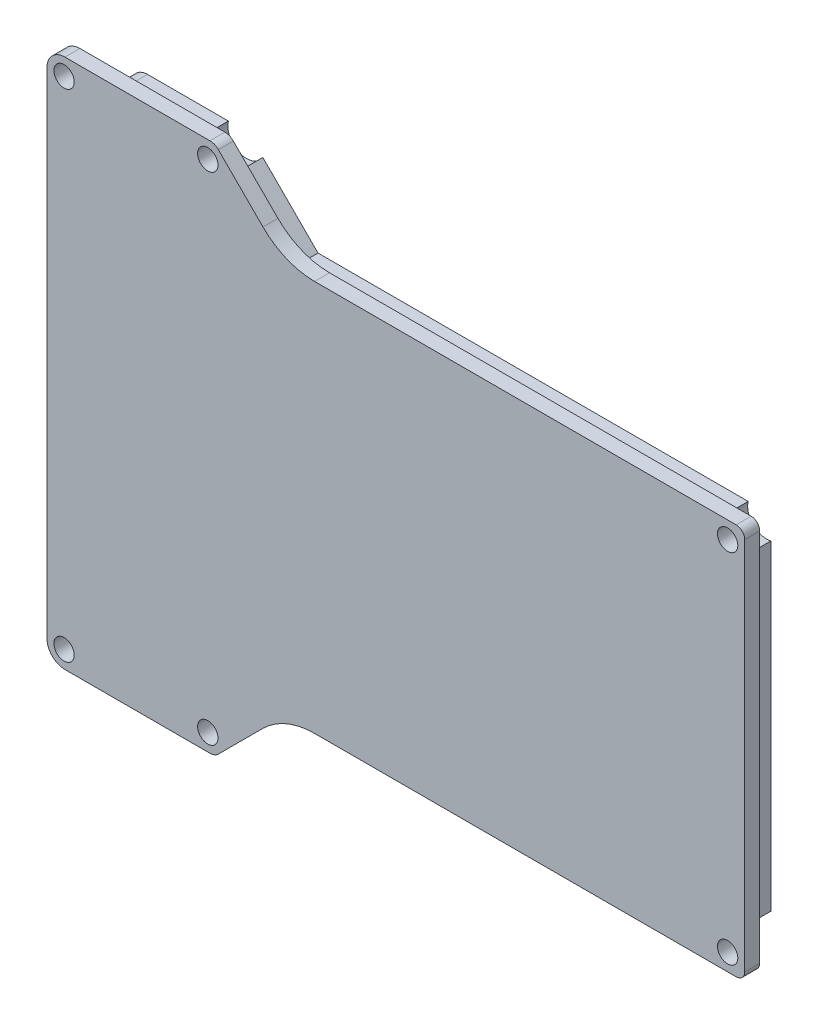
SolidWorks part; units mm, degrees
ref_plane "Front Plane" through (0, 0, 0) normal (0, 0, 1) x (1, 0, 0)
ref_plane "Top Plane" through (0, 0, 0) normal (0, 1, 0) x (1, 0, 0)
ref_plane "Right Plane" through (0, 0, 0) normal (1, 0, 0) x (0, 0, -1)
sketch "Sketch1" plane through (0, 0, 0) normal (0, 0, 1) x (1, 0, 0)
  line L0 (22, -44.3746) -> (2.3, -44.3746)
  line L1 (90.115, -44.3746) -> (105.155, -44.3746)
  line L2 (90.115, -68.9796) -> (22, -68.9796)
  line L3 (90.115, -44.8746) -> (22, -44.8746)
  line L4 (90.115, -44.3746) -> (22, -44.3746)
  line L5 (90.115, -69.4796) -> (22, -69.4796)
  line L6 (90.115, -69.4796) -> (105.155, -69.4796)
  line L7 (22, -69.4796) -> (2.3, -69.4796)
  line L8 (90.115, -42.3746) -> (105.155, -42.3746)
  line L9 (90.115, -42.3746) -> (22, -42.3746)
  line L10 (22, -42.3746) -> (2.3, -42.3746)
  line L11 (90.115, -71.4796) -> (105.155, -71.4796)
  line L12 (90.115, -71.4796) -> (22, -71.4796)
  line L13 (22, -71.4796) -> (2.3, -71.4796)
  line L14 (2.3, -44.3746) -> (2.3, -69.4796)
  line L15 (2.3, -71.4796) -> (2.3, -97.2696)
  line L16 (0, -18.2696) -> (0, -97.2696)
  line L17 (16.9123, -15.2696) -> (3, -15.2696)
  line L18 (31.605, -26.8746) -> (22.1833, -17.4529)
  line L19 (103.7528, -26.8746) -> (31.605, -26.8746)
  line L20 (107.455, -84.9574) -> (107.455, -30.5767)
  line L21 (31.61, -88.6596) -> (103.7528, -88.6596)
  line L22 (22.1833, -98.0863) -> (31.61, -88.6596)
  line L23 (3, -100.2696) -> (16.9123, -100.2696)
  line L24 (-4.3, -102.0736) -> (19.9188, -102.0736)
  line L25 (21.333, -101.4878) -> (28.7851, -94.0357)
  line L26 (37.409, -90.4636) -> (107.834, -90.4636)
  line L27 (109.259, -89.0386) -> (109.259, -26.4956)
  line L28 (107.834, -25.0706) -> (37.404, -25.0706)
  line L29 (28.7801, -21.4985) -> (21.333, -14.0514)
  line L30 (-7.3, -16.4656) -> (-7.3, -99.0736)
  line L31 (19.9188, -13.4656) -> (-4.3, -13.4656)
  line L32 (16.5027, -15.5696) -> (3, -15.5696)
  line L33 (0.3, -18.2696) -> (0.3, -97.2696)
  line L34 (3, -99.9696) -> (16.5027, -99.9696)
  line L35 (22.2608, -97.5845) -> (31.4857, -88.3596)
  line L36 (31.4857, -88.3596) -> (103.3433, -88.3596)
  line L37 (107.155, -84.5479) -> (107.155, -30.9863)
  line L38 (103.3433, -27.1746) -> (31.4807, -27.1746)
  line L39 (31.4807, -27.1746) -> (22.2608, -17.9547)
  line L40 (14.5666, -17.5696) -> (3, -17.5696)
  line L41 (2.3, -18.2696) -> (2.3, -42.3746)
  line L42 (3, -97.9696) -> (14.5666, -97.9696)
  line L43 (22.2156, -94.8013) -> (30.6573, -86.3596)
  line L44 (30.6573, -86.3596) -> (101.4072, -86.3596)
  line L45 (105.155, -82.6118) -> (105.155, -71.4796)
  line L46 (101.4072, -29.1746) -> (30.6523, -29.1746)
  line L47 (30.6523, -29.1746) -> (22.2156, -20.7379)
  line L48 (2.3, -18.2696) -> (2.3, -97.2696) construction
  line L49 (105.155, -42.3746) -> (105.155, -32.9224)
  line L50 (105.155, -69.4796) -> (105.155, -44.3746)
  line L51 (105.155, -82.6118) -> (105.155, -32.9224) construction
  circle A20 centre (106.406, -87.6106) radius 1.5
  circle A21 centre (106.406, -27.9236) radius 1.5
  circle A22 centre (19.5655, -16.3186) radius 1.5
  circle A23 centre (-4.447, -16.3186) radius 1.5
  circle A24 centre (19.5655, -99.2206) radius 1.5
  circle A25 centre (-4.447, -99.2206) radius 1.5
  arc A26 (3, -15.2696) -> (0, -18.2696) centre (3, -18.2696) ccw
  arc A27 (16.9123, -15.2696) -> (22.1833, -17.4529) centre (19.5655, -16.3186) ccw
  arc A28 (103.7528, -26.8746) -> (107.455, -30.5767) centre (106.406, -27.9236) ccw
  arc A29 (107.455, -84.9574) -> (103.7528, -88.6596) centre (106.406, -87.6106) ccw
  arc A30 (22.1833, -98.0863) -> (16.9123, -100.2696) centre (19.5655, -99.2206) ccw
  arc A31 (0, -97.2696) -> (3, -100.2696) centre (3, -97.2696) ccw
  arc A32 (-7.3, -99.0736) -> (-4.3, -102.0736) centre (-4.3, -99.0736) ccw
  arc A33 (19.9188, -102.0736) -> (21.333, -101.4878) centre (19.9188, -100.0736) ccw
  arc A34 (37.409, -90.4636) -> (28.7851, -94.0357) centre (37.409, -102.6596) ccw
  arc A35 (107.834, -90.4636) -> (109.259, -89.0386) centre (107.834, -89.0386) ccw
  arc A36 (109.259, -26.4956) -> (107.834, -25.0706) centre (107.834, -26.4956) ccw
  arc A37 (28.7801, -21.4985) -> (37.404, -25.0706) centre (37.404, -12.8746) ccw
  arc A38 (21.333, -14.0514) -> (19.9188, -13.4656) centre (19.9188, -15.4656) ccw
  arc A39 (-4.3, -13.4656) -> (-7.3, -16.4656) centre (-4.3, -16.4656) ccw
  arc A40 (3, -15.5696) -> (0.3, -18.2696) centre (3, -18.2696) ccw
  arc A41 (0.3, -97.2696) -> (3, -99.9696) centre (3, -97.2696) ccw
  arc A42 (22.2608, -97.5845) -> (16.5027, -99.9696) centre (19.5655, -99.2206) ccw
  arc A43 (107.155, -84.5479) -> (103.3433, -88.3596) centre (106.406, -87.6106) ccw
  arc A44 (103.3433, -27.1746) -> (107.155, -30.9863) centre (106.406, -27.9236) ccw
  arc A45 (16.5027, -15.5696) -> (22.2608, -17.9547) centre (19.5655, -16.3186) ccw
  arc A46 (3, -17.5696) -> (2.3, -18.2696) centre (3, -18.2696) ccw
  arc A47 (2.3, -97.2696) -> (3, -97.9696) centre (3, -97.2696) ccw
  arc A48 (22.2156, -94.8013) -> (14.5666, -97.9696) centre (19.5655, -99.2206) ccw
  arc A49 (105.155, -82.6118) -> (101.4072, -86.3596) centre (106.406, -87.6106) ccw
  arc A50 (101.4072, -29.1746) -> (105.155, -32.9224) centre (106.406, -27.9236) ccw
  arc A51 (14.5666, -17.5696) -> (22.2156, -20.7379) centre (19.5655, -16.3186) ccw
  dimension "D1" = 0.3
  dimension "D2" = 2
  dimension "D3" = 0.5
  dimension "D4" = 0.5
  dimension "D5" = 2
  dimension "D6" = 2
extrude "Boss-Extrude1" add sketch "Sketch1" along normal blind 2.5 contours L24 A33 L25 A34 L26 A35 L27 A36 L28 A37 L29 A38 L31 A39 L30 A32
extrude "Boss-Extrude2" add sketch "Sketch1<3>" against normal blind 4 contours A45 L32 A40 L33 A41 L34 A42 L35 L36 A43 L37 A44 L38 L39 L40 A51 L47 L46 A50 L45 A49 L44 L43 A48 L42 A47 L41 A46 region at (17.8378, -20.4896, 0)
sketch "Sketch1<3>" plane through (0, 0, 0) normal (0, 0, 1) x (1, 0, 0) same geometry as "Sketch1"
sketch "Sketch2" plane through (0, 0, 2.5) normal (0, 0, 1) x (1, 0, 0)
  circle A0 centre (19.5655, -99.2206) radius 1.5 construction
  circle A1 centre (-4.447, -99.2206) radius 1.5 construction
  circle A2 centre (19.5655, -16.3186) radius 1.5 construction
  circle A3 centre (-4.447, -16.3186) radius 1.5 construction
  circle A4 centre (106.406, -87.6106) radius 1.5 construction
  circle A5 centre (106.406, -27.9236) radius 1.5 construction
  circle A6 centre (19.5655, -99.2206) radius 1.5
  circle A7 centre (-4.447, -99.2206) radius 1.5
  circle A8 centre (19.5655, -16.3186) radius 1.5
  circle A9 centre (-4.447, -16.3186) radius 1.5
  circle A10 centre (106.406, -87.6106) radius 1.5
  circle A11 centre (106.406, -27.9236) radius 1.5
  circle A12 centre (106.406, -87.6106) radius 1.7
  circle A13 centre (106.406, -27.9236) radius 1.7
  circle A14 centre (-4.447, -16.3186) radius 1.7
  circle A15 centre (19.5655, -16.3186) radius 1.7
  circle A16 centre (19.5655, -99.2206) radius 1.7
  circle A17 centre (-4.447, -99.2206) radius 1.7
  dimension "D1" = 0.2
extrude "Cut-Extrude1" cut sketch "Sketch2" against normal blind 10 contours A17 | A16 | A14 | A15 | A13 | A12
